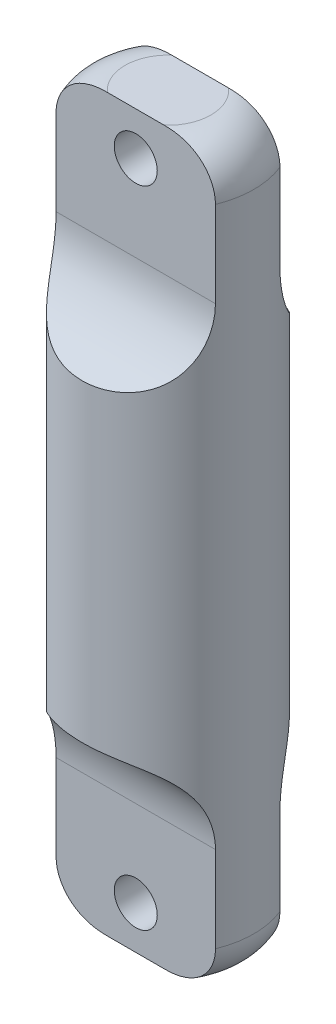
SolidWorks part; units mm, degrees
ref_plane "Front Plane" through (0, 0, 0) normal (0, 0, 1) x (1, 0, 0)
ref_plane "Top Plane" through (0, 0, 0) normal (0, 1, 0) x (1, 0, 0)
ref_plane "Right Plane" through (0, 0, 0) normal (1, 0, 0) x (0, 0, -1)
sketch "Sketch1" plane through (0, 0, 0) normal (0, 1, 0) x (1, 0, 0)
  circle A0 centre (0, 0) radius 12.7
  dimension "D1" = 25.4
extrude "Boss-Extrude1" add sketch "Sketch1" along normal blind 107.95
ref_plane "Plane1" through (12.7, 0, 0) normal (1, 0, 0) x (0, 0, -1)
sketch "Sketch2" plane through (12.7, 0, 0) normal (1, 0, 0) x (0, 0, -1)
  line L0 (12.7, 107.95) -> (-12.7, 107.95) construction
  line L1 (12.7, 107.95) -> (4.7625, 107.95)
  line L2 (12.7, 107.95) -> (12.7, 76.2)
  line L3 (4.7625, 107.95) -> (4.7625, 76.2)
  line L4 (4.7625, 76.2) -> (12.7, 76.2)
  line L5 (-4.7625, 107.95) -> (-4.7625, 76.2)
  line L6 (-4.7625, 76.2) -> (-12.7, 76.2)
  line L7 (-12.7, 76.2) -> (-12.7, 107.95)
  line L8 (-4.7625, 107.95) -> (-12.7, 107.95)
  dimension "D1" = 9.525
  dimension "D2" = 31.75
extrude "Cut-Extrude1" cut sketch "Sketch2" against normal through all
fillet "Fillet1" radius 12.7 2 edges at (0, 76.2, 4.7625) (0, 76.2, -4.7625)
ref_plane "Plane2" through (0, 53.975, 0) normal (0, 1, 0) x (1, 0, 0)
mirror "Mirror1" about plane through (0, 53.975, 0) normal (0, 1, 0) of "Cut-Extrude1", "Fillet1"
hole_wizard "Hole1" positions "Sketch3" profile "Sketch4" legacy end condition through all
sketch "Sketch3" plane through (0, 0, 4.7625) normal (0, 0, 1) x (1, 0, 0)
  line L0 (0, 101.6) -> (0, 6.35)
  line L2 (13.97, 53.975) -> (-13.97, 53.975) construction
  line L3 (0, 101.6) -> (0, 107.95) construction
  line L4 (11.7732, 107.95) -> (-11.7732, 107.95) construction
  point P0 (0, 101.6)
  point P2 (0, 6.35)
  point P10 (0, 53.975)
  dimension "D1" = 95.25
sketch "Sketch4" plane through (0, 101.6, 4.7625) normal (1, 0, 0) x (0, -1, 0)
  line L0 (0, 0) -> (0, 17.4625)
  line L1 (0, 17.4625) -> (3.175, 17.4625)
  line L2 (3.175, 17.4625) -> (3.175, 0)
  line L3 (3.175, 0) -> (0, 0)
  line L4 (0, 110) -> (0, -10) construction
  dimension "Diameter" = 6.35
  dimension "Depth" = 17.4625
fillet "Fillet6" radius 6.35 4 edges at (12.7, 107.95, 0) (-12.7, 107.95, 0) (-12.7, 0, 0) (12.7, 0, 0)
